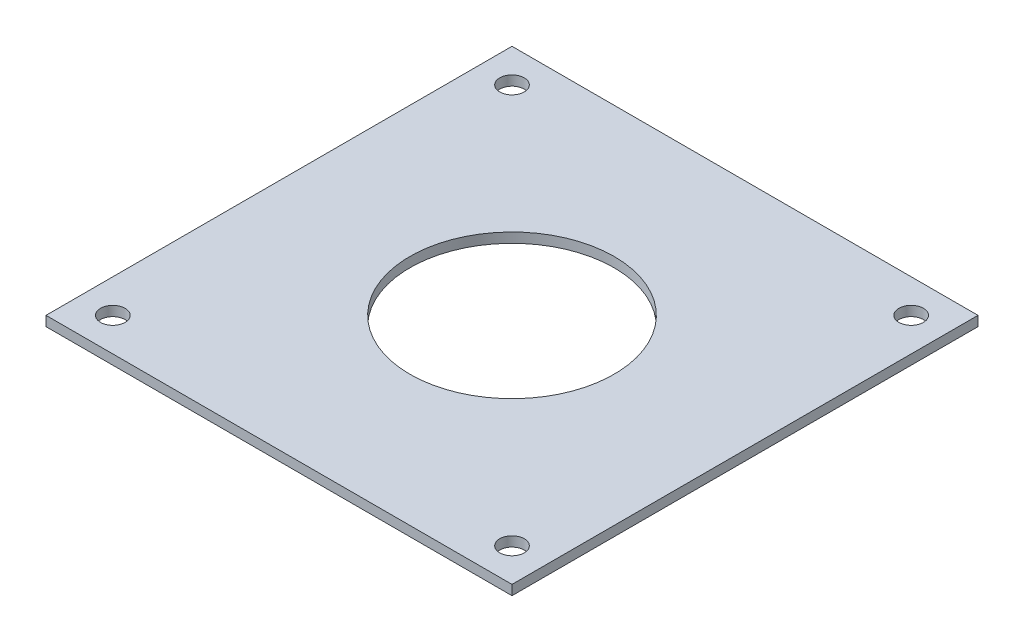
SolidWorks part; units mm, degrees
ref_plane "Front Plane" through (0, 0, 0) normal (0, 0, 1) x (1, 0, 0)
ref_plane "Top Plane" through (0, 0, 0) normal (0, 1, 0) x (1, 0, 0)
ref_plane "Right Plane" through (0, 0, 0) normal (1, 0, 0) x (0, 0, -1)
sketch "Sketch1" plane through (0, 0, 0) normal (0, 1, 0) x (1, 0, 0)
  line L1 (-38, -38) -> (38, -38)
  line L2 (-38, -38) -> (-38, 38)
  line L3 (-38, 38) -> (38, 38)
  line L4 (38, -38) -> (38, 38)
  line L5 (-38, -38) -> (38, 38) construction
  line L6 (-38, 38) -> (38, -38) construction
  circle A0 centre (32.55, 32.55) radius 2
  circle A1 centre (0, 0) radius 16.65
  circle A2 centre (32.55, -32.55) radius 2
  circle A3 centre (-32.55, -32.55) radius 2
  circle A4 centre (-32.55, 32.55) radius 2
  point P0 (0, 0)
  dimension "D4" = 4
  dimension "D5" = 33.3
  dimension "D6" = 4
  dimension "D7" = 4
  dimension "D8" = 4
  dimension "D1" = 76
  dimension "D2" = 76
  dimension "D3" = 5.45
  dimension "D9" = 5.45
  dimension "D10" = 5.45
  dimension "D11" = 5.45
base flange "Base-Flange1" sketch "Sketch1" thickness 1.6 reverse thickness direction no parameters "D1"=0.6
sketch "Bend-Lines1" plane through (0, 0, 0) normal (0, 1, 0) x (1, 0, 0)
sketch "Bounding-Box1" plane through (0, 0, 0) normal (0, 1, 0) x (1, 0, 0)
sheet metal parameters "Sheet-Metal(1)" thickness 1.6 parameters "D1"=0.6
flat pattern "Flat-Pattern(1)" [suppressed]
sketch "Bend-Lines2" plane through (0, 0, 0) normal (0, 1, 0) x (1, 0, 0)
sketch "Bounding-Box2" [suppressed] plane through (0, 0, 0) normal (0, 1, 0) x (1, 0, 0)
